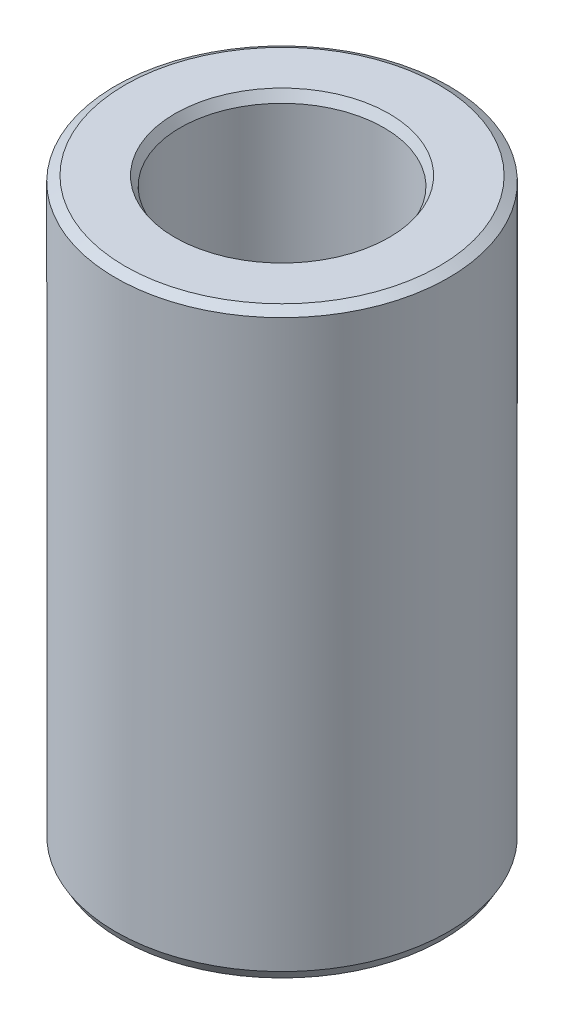
SolidWorks part; units mm, degrees
ref_plane "Front Plane" through (0, 0, 0) normal (0, 0, 1) x (1, 0, 0)
ref_plane "Top Plane" through (0, 0, 0) normal (0, 1, 0) x (1, 0, 0)
ref_plane "Right Plane" through (0, 0, 0) normal (1, 0, 0) x (0, 0, -1)
sketch "Sketch1" plane through (0, 0, 0) normal (0, 1, 0) x (1, 0, 0)
  circle A0 centre (0, 0) radius 45
  dimension "SLEEVE_OD" = 90
extrude "Boss-Extrude1" add sketch "Sketch1" along normal blind 157.1339
sketch "Sketch2" plane through (0, 0, 0) normal (0, 1, 0) x (1, 0, 0)
  circle A0 centre (0, 0) radius 27.5239
  dimension "BORE_D" = 55.0479
extrude "Cut-Extrude1" cut sketch "Sketch2" along normal through all
chamfer "Chamfer1" distance 1.4628 angle 60 4 edges at (0, 157.1339, 27.5239) (0, 0, 27.5239) (0, 0, 45) (0, 157.1339, 45) first distance on face at (0, 157.1339, 27.5239) first distance on face at (0, 0, 27.5239) first distance on face at (0, 157.1339, 45)
